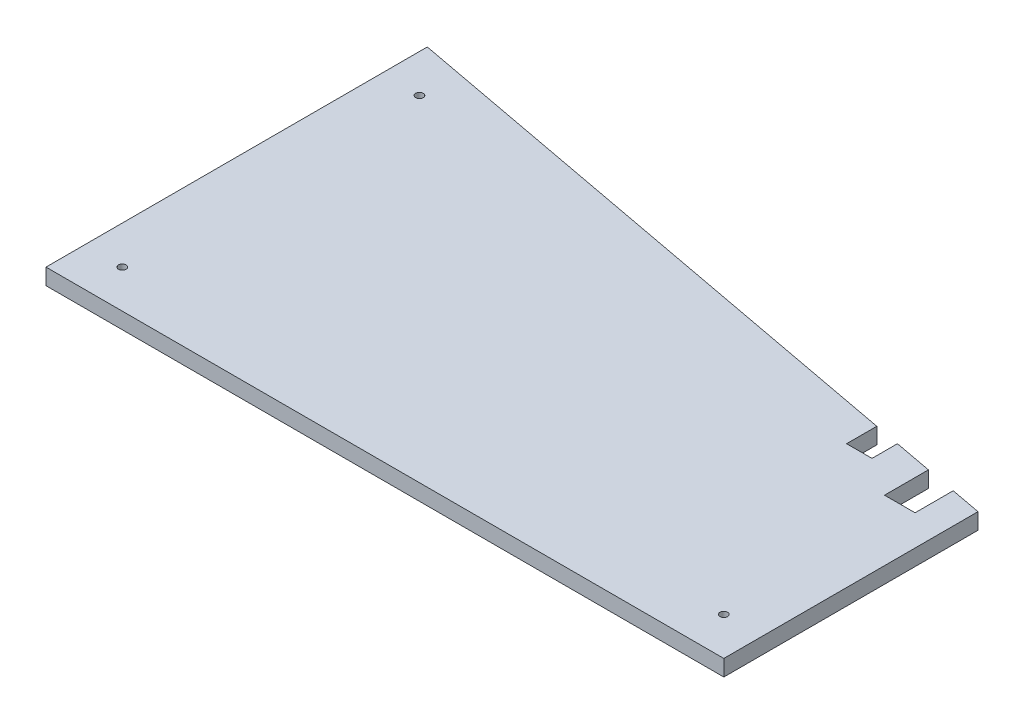
SolidWorks part; units mm, degrees
material "Balsa"
ref_plane "Front Plane" through (0, 0, 0) normal (0, 0, 1) x (1, 0, 0)
ref_plane "Top Plane" through (0, 0, 0) normal (0, 1, 0) x (1, 0, 0)
ref_plane "Right Plane" through (0, 0, 0) normal (1, 0, 0) x (0, 0, -1)
sketch "Sketch2" plane through (0, 0, 0) normal (0, 1, 0) x (1, 0, 0)
  line L0 (0, 0) -> (266.65, 0)
  line L1 (266.65, 0) -> (266.65, 100)
  line L2 (266.65, 100) -> (254.65, 102.2501)
  line L4 (242.6501, 104.5003) -> (242.6501, 87.2152)
  line L5 (242.6501, 87.2152) -> (254.65, 87.2501)
  line L6 (254.65, 87.2501) -> (254.65, 102.2501)
  line L7 (242.6501, 104.5003) -> (227.6501, 107.3129)
  line L8 (227.6501, 97.3129) -> (217.6501, 97.2838)
  line L9 (217.6501, 97.2838) -> (217.6501, 109.1881)
  line L10 (227.6501, 97.3129) -> (227.6501, 107.3129)
  line L11 (217.6501, 109.1881) -> (0, 150)
  line L16 (0, 150) -> (0, 0)
  point P10 (0, 0)
  point P12 (0, 0)
  point P15 (0, 0)
  dimension "D1" = 150
  dimension "D2" = 100
  dimension "D3" = 266.65
  dimension "D4" = 12
  dimension "D5" = 12
  dimension "D6" = 15
  dimension "D7" = 10
  dimension "D8" = 10
  dimension "D9" = 15
  dimension "D10" = 11.9042
  dimension "D11" = 17.2851
extrude "Boss-Extrude1" add sketch "Sketch2" along normal blind 6.35
sketch "Sketch3" plane through (0, 6.35, 0) normal (0, 1, 0) x (1, 0, 0)
  line L0 (0, 0) -> (266.65, 0) construction
  line L1 (0, 150) -> (0, 0) construction
  line L3 (217.6501, 109.1881) -> (0, 150) construction
  line L4 (266.65, 0) -> (266.65, 100) construction
  circle A0 centre (15, 131.9259) radius 1.5
  circle A1 centre (15, 15) radius 1.5
  circle A2 centre (251.65, 15) radius 1.5
  point P6 (0, 0)
  point P13 (15.4839, 147.0966)
  dimension "D1" = 3
  dimension "D2" = 3
  dimension "D3" = 3
  dimension "D4" = 15
  dimension "D5" = 15
  dimension "D6" = 15
  dimension "D7" = 15
  dimension "D8" = 15
  dimension "D9" = 15
extrude "Cut-Extrude1" cut sketch "Sketch3" against normal through all
